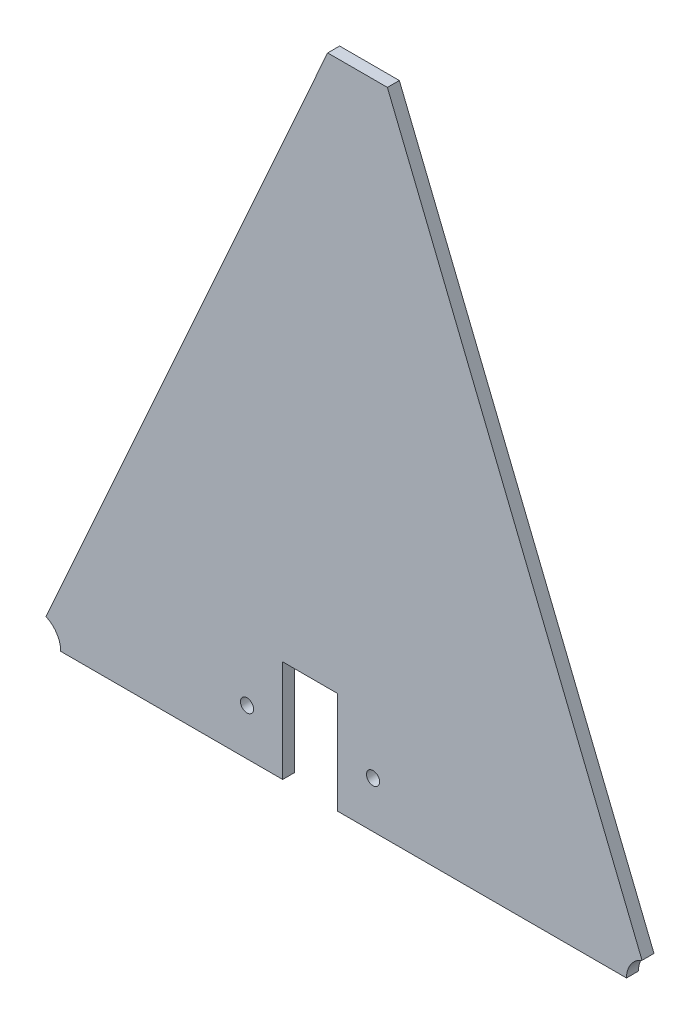
SolidWorks part; units mm, degrees
ref_plane "Front Plane" through (0, 0, 0) normal (0, 0, 1) x (1, 0, 0)
ref_plane "Top Plane" through (0, 0, 0) normal (0, 1, 0) x (1, 0, 0)
ref_plane "Right Plane" through (0, 0, 0) normal (1, 0, 0) x (0, 0, -1)
sketch "Sketch2" plane through (0, 0, 0) normal (0, 0, 1) x (1, 0, 0)
  line L0 (-189.7401, 245.3834) -> (-375.9085, -170.4146)
  line L1 (-375.9085, -170.4146) -> (16.7755, -170.4146)
  line L2 (16.7755, -170.4146) -> (-151.6401, 245.3834)
  line L4 (-189.7401, 245.3834) -> (-151.6401, 245.3834)
  dimension "D1" = 415.798
  dimension "D2" = 415.798
  dimension "D3" = 67.95
  dimension "D4" = 38.1
  dimension "D5" = 392.684
extrude "Boss-Extrude1" add sketch "Sketch2" along normal blind 7.62 contours L0 L1 L2 L4
sketch "Sketch5" plane through (0, 0, 0) normal (0, 0, -1) x (-1, 0, 0)
  circle A0 centre (375.9085, -170.4146) radius 15.875
  dimension "D1" = 31.75
extrude "Cut-Extrude2" cut sketch "Sketch5" against normal blind 50.8
sketch "Sketch6" plane through (0, 0, 0) normal (0, 0, -1) x (-1, 0, 0)
  circle A0 centre (-16.7755, -170.4146) radius 15.875
  dimension "D1" = 31.75
extrude "Cut-Extrude3" cut sketch "Sketch6" against normal blind 50.8 contours A0
ref_plane "Plane1" through (-360.0335, -170.4146, 0) normal (1, 0, 0) x (0, 0, -1)
sketch "Sketch8" plane through (0, 0, 0) normal (0, 0, -1) x (-1, 0, 0)
  line L0 (254.9716, -43.4146) -> (147.0216, -43.4146) construction
  line L1 (360.0335, -170.4146) -> (-0.9005, -170.4146) construction
  line L2 (254.9716, -170.4146) -> (254.9716, 97.7332) construction
  line L3 (254.9716, -43.4146) -> (254.9716, -170.4146) construction
  line L4 (147.0216, -43.4146) -> (147.0216, -170.4146) construction
  line L5 (147.0216, -170.4146) -> (183.5239, -170.4146) construction
  line L6 (183.5239, -170.4146) -> (183.5239, -105.3906) construction
  line L7 (170.6901, 245.3834) -> (179.5665, -170.4146) construction
  line L8 (189.7401, 245.3834) -> (151.6401, 245.3834) construction
  line L9 (183.5239, -105.3906) -> (218.4489, -105.3906) construction
  line L10 (218.4489, -105.3906) -> (218.4489, -170.4146) construction
  line L11 (218.4489, -170.4146) -> (218.4489, -105.3906)
  line L12 (218.4489, -105.3906) -> (183.5239, -105.3906)
  line L13 (183.5239, -105.3906) -> (183.5239, -170.4146)
  line L14 (153.8492, -170.4146) -> (153.8492, -48.647) construction
  dimension "D1" = 268.1478
  dimension "D2" = 107.95
  dimension "D3" = 127
  dimension "D4" = 36.5023
  dimension "D5" = 65.024
  dimension "D6" = 34.925
  dimension "D7" = 121.7676
extrude "Cut-Extrude4" cut sketch "Sketch8" against normal blind 7.62 and the other way through all contours L11 L12 L13
sketch "Sketch9" plane through (0, 0, 0) normal (0, 0, -1) x (-1, 0, 0)
  line L0 (164.9819, -140.8236) -> (183.5239, -140.8236) construction
  line L1 (183.5239, -170.4146) -> (183.5239, -105.3906) construction
  line L2 (160.7909, -145.0146) -> (160.7909, -170.4146) construction
  line L3 (183.5239, -170.4146) -> (-0.9005, -170.4146) construction
  line L4 (236.9909, -140.8236) -> (218.4489, -140.8236) construction
  line L5 (218.4489, -105.3906) -> (218.4489, -170.4146) construction
  line L6 (241.1819, -145.0146) -> (241.1819, -170.4146) construction
  line L7 (360.0335, -170.4146) -> (218.4489, -170.4146) construction
  circle A0 centre (160.7909, -140.8236) radius 4.191
  circle A1 centre (241.1819, -140.8236) radius 4.191
  point P20 (0, 0)
  point P21 (0, 0)
  point P22 (0, 0)
  point P23 (0, 0)
  point P24 (0, 0)
  dimension "D3" = 8.382
  dimension "D6" = 8.382
  dimension "D1" = 18.542
  dimension "D2" = 25.4
  dimension "D4" = 18.542
  dimension "D5" = 25.4
sketch "Sketch10" plane through (0, 0, 0) normal (0, 0, -1) x (-1, 0, 0)
  line L0 (218.4489, -110.7541) -> (349.1963, -110.7541) construction
  line L1 (218.4489, -105.3906) -> (218.4489, -170.4146) construction
  line L2 (189.7401, 245.3834) -> (369.4213, -155.9256) construction
  line L3 (7.3895, -110.7541) -> (138.1995, -110.7541) construction
  line L4 (-10.8158, -155.7008) -> (151.6401, 245.3834) construction
  dimension "D1" = 130.7473
  dimension "D2" = 130.81
extrude "Cut-Extrude6" cut sketch "Sketch9" against normal up to next
